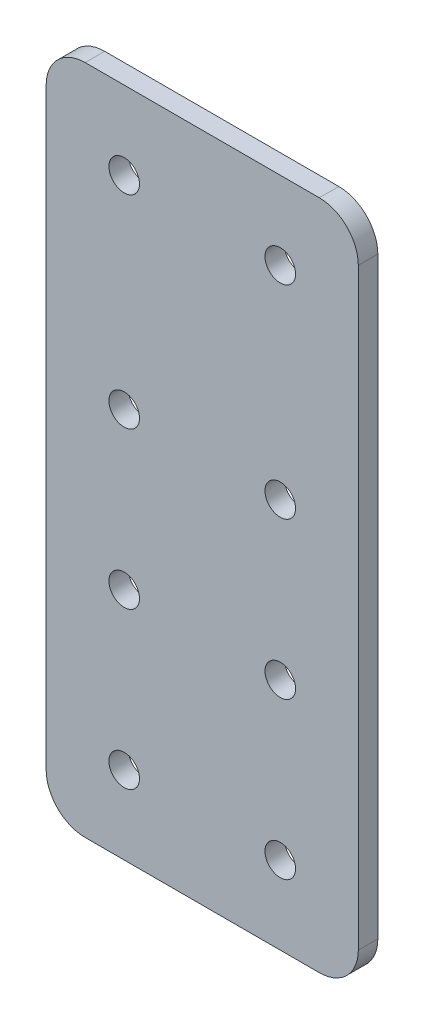
SolidWorks part; units mm, degrees
material "6061-T6 (SS)"
ref_plane "Front Plane" through (0, 0, 0) normal (0, 0, 1) x (1, 0, 0)
ref_plane "Top Plane" through (0, 0, 0) normal (0, 1, 0) x (1, 0, 0)
ref_plane "Right Plane" through (0, 0, 0) normal (1, 0, 0) x (0, 0, -1)
sketch "Sketch2" plane through (0, 0, 0) normal (0, 0, 1) x (1, 0, 0)
  line L1 (0, 0) -> (50.8, 0)
  line L2 (0, 0) -> (0, 109.22)
  line L3 (0, 109.22) -> (50.8, 109.22)
  line L6 (50.8, 109.22) -> (50.8, 0)
  dimension "D1" = 50.8
  dimension "D2" = 109.22
extrude "Boss-Extrude1" add sketch "Sketch2" against normal blind 3.175
sketch "Sketch3" plane through (0, 0, 0) normal (0, 0, 1) x (1, 0, 0)
  line L0 (50.8, 109.22) -> (0, 109.22) construction
  line L1 (0, 109.22) -> (0, 0) construction
  circle A0 centre (12.7, 96.52) radius 2.4892
  circle A17 centre (38.1, 96.52) radius 2.4892
  circle A24 centre (12.7, 63.5) radius 2.4892
  circle A25 centre (12.7, 38.1) radius 2.4892
  circle A26 centre (12.7, 12.7) radius 2.4892
  circle A27 centre (12.7, -12.7) radius 2.4892
  circle A28 centre (12.7, -38.1) radius 2.4892
  circle A33 centre (38.1, 38.1) radius 2.4892
  circle A34 centre (38.1, 12.7) radius 2.4892
  circle A35 centre (38.1, -12.7) radius 2.4892
  circle A36 centre (38.1, -38.1) radius 2.4892
  circle A41 centre (38.1, 63.5) radius 2.4892
  dimension "D1" = 4.9784
  dimension "D6" = 4.9784
  dimension "D2" = 12.7
  dimension "D3" = 12.7
  dimension "D7" = 12.7
  dimension "D8" = 33.02
  dimension "D4" = 1
  dimension "D5" = 2
  dimension "D9" = 5
  dimension "D10" = 2
extrude "Cut-Extrude1" cut sketch "Sketch3" against normal through all
fillet "Fillet1" radius 6.35 4 edges at (0, 0, -1.5875) (0, 109.22, -1.5875) (50.8, 0, -1.5875) (50.8, 109.22, -1.5875)
